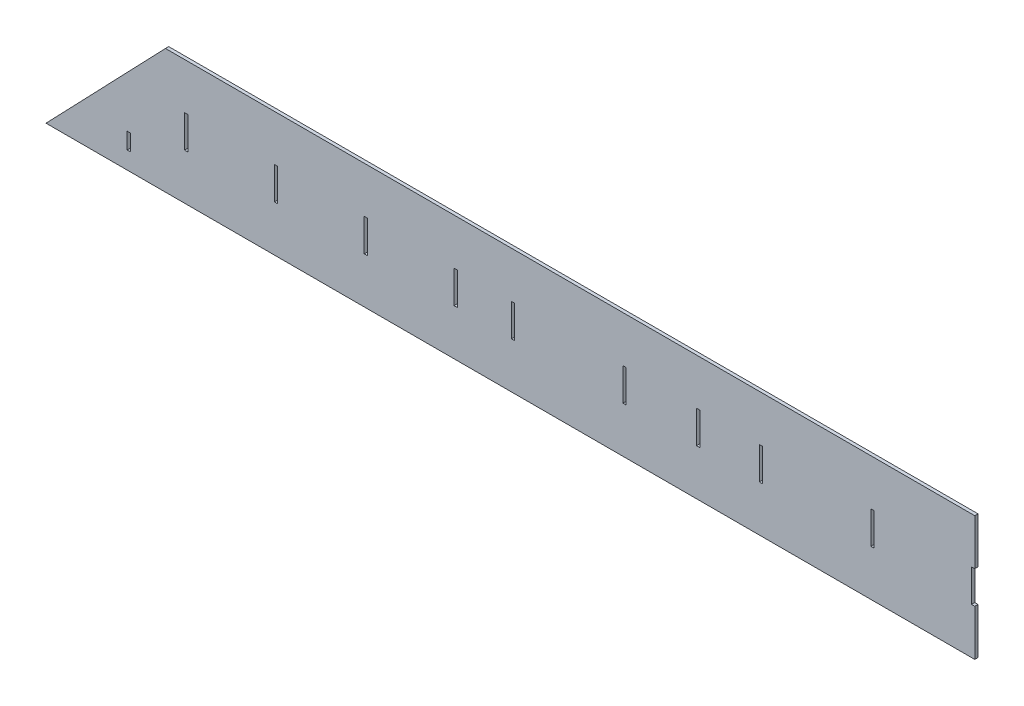
SolidWorks part; units mm, degrees
ref_plane "Front Plane" through (0, 0, 0) normal (0, 0, 1) x (1, 0, 0)
ref_plane "Top Plane" through (0, 0, 0) normal (0, 1, 0) x (1, 0, 0)
ref_plane "Right Plane" through (0, 0, 0) normal (1, 0, 0) x (0, 0, -1)
sketch "Sketch1" plane through (0, 0, 0) normal (0, 0, 1) x (1, 0, 0)
  line L0 (0, 0) -> (110.3511, 115)
  line L1 (110.3511, 115) -> (858, 115)
  line L3 (858, 0) -> (0, 0)
  line L4 (1244.614, 57.5) -> (-683.0281, 57.5) construction
  line L5 (128, 72.5) -> (131, 72.5)
  line L6 (128, 72.5) -> (128, 42.5)
  line L7 (128, 42.5) -> (131, 42.5)
  line L8 (131, 72.5) -> (131, 42.5)
  line L9 (75, 31.1091) -> (78, 31.1091)
  line L10 (75, 31.1091) -> (75, 16.1091)
  line L11 (75, 16.1091) -> (78, 16.1091)
  line L12 (78, 31.1091) -> (78, 16.1091)
  line L14 (211, 72.5) -> (214, 72.5)
  line L15 (211, 72.5) -> (211, 42.5)
  line L16 (211, 42.5) -> (214, 42.5)
  line L17 (214, 72.5) -> (214, 42.5)
  line L18 (294, 72.5) -> (297, 72.5)
  line L19 (294, 72.5) -> (294, 42.5)
  line L20 (294, 42.5) -> (297, 42.5)
  line L21 (297, 72.5) -> (297, 42.5)
  line L22 (377, 72.5) -> (380, 72.5)
  line L23 (377, 72.5) -> (377, 42.5)
  line L24 (377, 42.5) -> (380, 42.5)
  line L25 (380, 72.5) -> (380, 42.5)
  line L26 (430, 72.5) -> (433, 72.5)
  line L27 (430, 72.5) -> (430, 42.5)
  line L28 (430, 42.5) -> (433, 42.5)
  line L29 (433, 72.5) -> (433, 42.5)
  line L30 (533, 72.5) -> (536, 72.5)
  line L31 (533, 72.5) -> (533, 42.5)
  line L32 (533, 42.5) -> (536, 42.5)
  line L33 (536, 72.5) -> (536, 42.5)
  line L34 (601, 72.5) -> (604, 72.5)
  line L35 (601, 72.5) -> (601, 42.5)
  line L36 (601, 42.5) -> (604, 42.5)
  line L37 (604, 72.5) -> (604, 42.5)
  line L38 (659, 72.5) -> (662, 72.5)
  line L39 (659, 72.5) -> (659, 42.5)
  line L40 (659, 42.5) -> (662, 42.5)
  line L41 (662, 72.5) -> (662, 42.5)
  line L42 (762, 72.5) -> (765, 72.5)
  line L43 (762, 72.5) -> (762, 42.5)
  line L44 (762, 42.5) -> (765, 42.5)
  line L45 (765, 72.5) -> (765, 42.5)
  line L46 (855, 72.5) -> (858, 72.5)
  line L47 (855, 72.5) -> (855, 42.5)
  line L48 (855, 42.5) -> (858, 42.5)
  line L53 (858, 72.5) -> (858, 115)
  line L54 (858, 42.5) -> (858, 0)
  dimension "D1" = 115
  dimension "D2" = 30
  dimension "D3" = 3
  dimension "D4" = 15
  dimension "D5" = 3
  dimension "D6" = 75
  dimension "D7" = 50
  dimension "D8" = 30
  dimension "D9" = 3
  dimension "D10" = 30
  dimension "D11" = 3
  dimension "D12" = 80
  dimension "D13" = 80
  dimension "D14" = 80
  dimension "D15" = 3
  dimension "D16" = 30
  dimension "D17" = 50
  dimension "D18" = 3
  dimension "D19" = 30
  dimension "D20" = 100
  dimension "D21" = 3
  dimension "D22" = 30
  dimension "D23" = 65
  dimension "D24" = 30
  dimension "D25" = 3
  dimension "D26" = 55
  dimension "D27" = 3
  dimension "D28" = 30
  dimension "D29" = 3
  dimension "D30" = 30
  dimension "D31" = 100
  dimension "D32" = 90
  dimension "D33" = 3
  dimension "D34" = 30
extrude "Boss-Extrude1" add sketch "Sketch1" along normal blind 3
